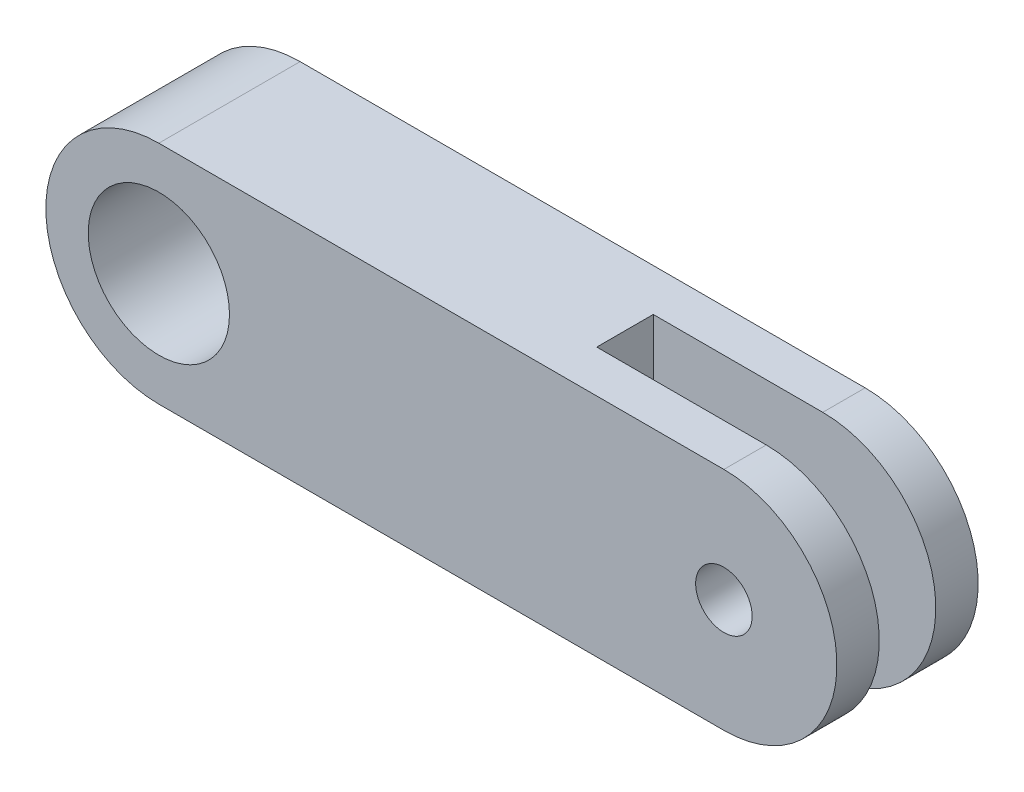
SolidWorks part; units mm, degrees
ref_plane "Front Plane" through (0, 0, 0) normal (0, 0, 1) x (1, 0, 0)
ref_plane "Top Plane" through (0, 0, 0) normal (0, 1, 0) x (1, 0, 0)
ref_plane "Right Plane" through (0, 0, 0) normal (1, 0, 0) x (0, 0, -1)
sketch "Sketch1" plane through (0, 0, 0) normal (0, 0, 1) x (1, 0, 0)
  line L0 (-10, 0) -> (10, 0) construction
  line L1 (-10, 4) -> (10, 4)
  line L2 (-10, -4) -> (10, -4)
  arc A0 (-10, 4) -> (-10, -4) centre (-10, 0) ccw
  arc A1 (10, -4) -> (10, 4) centre (10, 0) ccw
  circle A2 centre (-10, 0) radius 2.5
  circle A3 centre (10, 0) radius 1
  point P3 (0, 0)
  point P12 (0, 0)
  dimension "D1" = 5
  dimension "D2" = 4
  dimension "D4" = 2
  dimension "D3" = 20
extrude "Boss-Extrude1" add sketch "Sketch1" along normal mid plane 5
sketch "Sketch5" plane through (0, 0, 0) normal (0, 0, 1) x (1, 0, 0)
  line L0 (10, 4) -> (-10, 4) construction
  line L1 (4, 4) -> (14, 4)
  line L2 (4, 4) -> (4, -4)
  line L3 (4, -4) -> (14, -4)
  line L4 (14, 4) -> (14, -4)
  line L5 (-10, -4) -> (10, -4) construction
  arc A0 (10, -4) -> (10, 4) centre (10, 0) ccw construction
  dimension "D1" = 10
extrude "Cut-Extrude1" cut sketch "Sketch5" against normal mid plane 2
